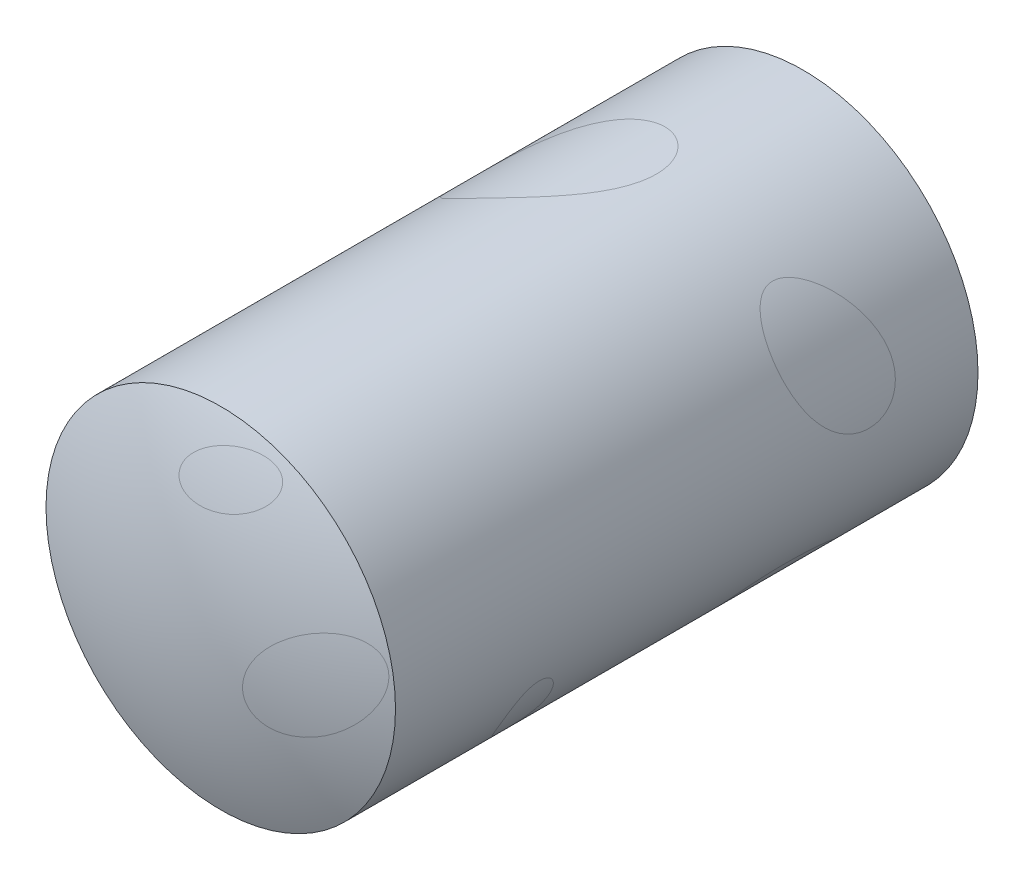
SolidWorks part; units mm, degrees
material "AISI 316 Annealed Stainless Steel Bar (SS)"
ref_plane "Front Plane" through (0, 0, 0) normal (0, 0, 1) x (1, 0, 0)
ref_plane "Top Plane" through (0, 0, 0) normal (0, 1, 0) x (1, 0, 0)
ref_plane "Right Plane" through (0, 0, 0) normal (1, 0, 0) x (0, 0, -1)
sketch "Sketch2" plane through (0, 0, 0) normal (0, 0, 1) x (1, 0, 0)
  circle A0 centre (0, 0) radius 6000
  dimension "D1" = 12000
extrude "Boss-Extrude1" add sketch "Sketch2" along normal blind 20000
dome "Dome1" faces to dome 1 distance 1200 reverse direction no elliptical dome no face at (6000, 0, 20000) parameters "D1"=1200
ref_plane "Plane5" through (0, 0, 50) normal (0, 0, 1) x (1, 0, 0)
ref_plane "Plane6" through (0, 0, 25000) normal (0, 0, 1) x (1, 0, 0)
sketch "Sketch8" plane through (0, 0, 50) normal (0, 0, 1) x (1, 0, 0)
  circle A0 centre (0, 0) radius 5950
extrude "Cut-Extrude2" cut sketch "Sketch8" along normal blind 19950
ref_plane "Plane7" through (10000, 0, 0) normal (1, 0, 0) x (0, 0, -1)
sketch "Sketch9" plane through (10000, 0, 0) normal (1, 0, 0) x (0, 0, -1)
  ellipse E0 centre (-14725.3504, -3057.2722) end of major axis (-14725.3504, -1959.2383) minor radius 803.2348
  point P1 (-13552.4397, -3242.1101)
split line "Split Line5"
sketch "Sketch10" plane through (0, 0, 25000) normal (0, 0, 1) x (1, 0, 0)
  ellipse E0 centre (3816.586, -64.8652) end of major axis (5638.8812, 1406.3456) minor radius 1321.2173
split line "Split Line6"
sketch "Sketch11" plane through (10000, 0, 0) normal (1, 0, 0) x (0, 0, -1)
  ellipse E0 centre (-4454.9047, 2290.2815) end of major axis (-3184.1439, 372.588) minor radius 1443.1026
split line "Split Line7"
ref_plane "Plane8" through (0, 10000, 0) normal (0, 1, 0) x (1, 0, 0)
sketch "Sketch12" plane through (0, 10000, 0) normal (0, 1, 0) x (1, 0, 0)
  ellipse E0 centre (-1849.5034, -6528.9172) end of major axis (45.4272, -4349.747) minor radius 1948.2871
split line "Split Line8"
sketch "Sketch13" plane through (10000, 0, 0) normal (1, 0, 0) x (0, 0, -1)
  ellipse E0 centre (-5156.9883, -4278.5897) end of major axis (-3181.2413, -4451.4676) minor radius 800.5147
split line "Split Line9"
sketch "Sketch14" plane through (0, 0, 25000) normal (0, 0, 1) x (1, 0, 0)
  ellipse E0 centre (784.0046, 4456.9781) end of major axis (-740.0606, 3882.075) minor radius 824.21
split line "Split Line10"
